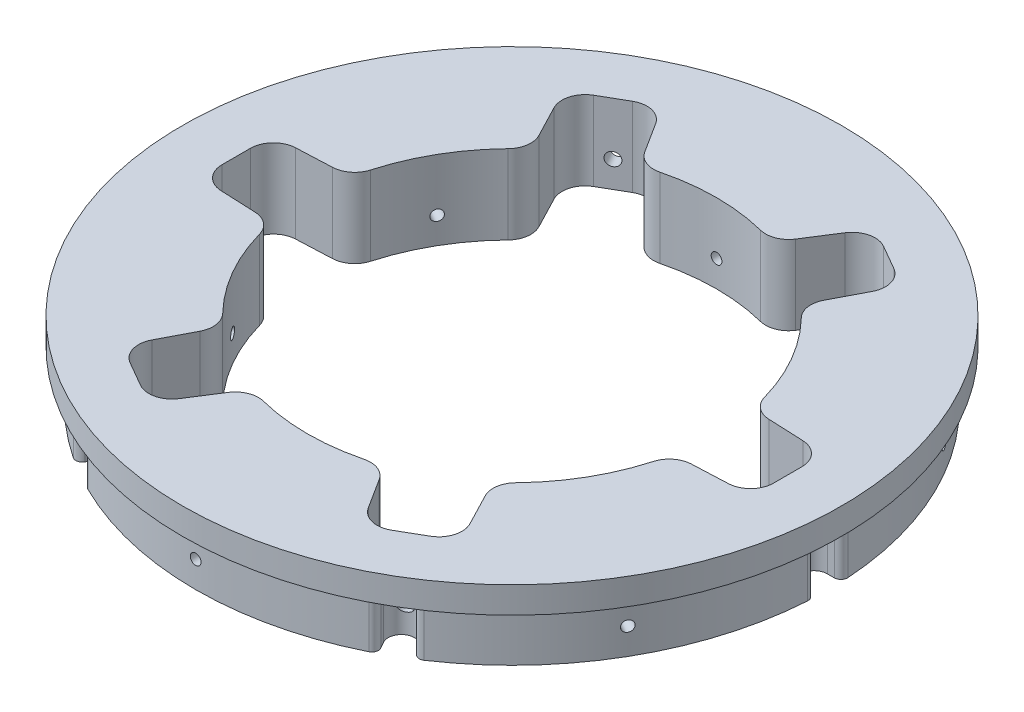
SolidWorks part; units mm, degrees
material "6061-T6 (SS)"
ref_plane "Front Plane" through (0, 0, 0) normal (0, 0, 1) x (1, 0, 0)
ref_plane "Top Plane" through (0, 0, 0) normal (0, 1, 0) x (1, 0, 0)
ref_plane "Right Plane" through (0, 0, 0) normal (1, 0, 0) x (0, 0, -1)
sketch "Sketch1" plane through (0, 0, 0) normal (0, 1, 0) x (1, 0, 0)
  circle A0 centre (0, 0) radius 76.2
  circle A1 centre (0, 0) radius 49.276
  dimension "D1" = 152.4
  dimension "D2" = 98.552
extrude "Boss-Extrude1" add sketch "Sketch1" against normal blind 19.05
sketch "Sketch3" plane through (0, -19.05, 0) normal (0, -1, 0) x (-1, 0, 0)
  line L0 (-76.1338, 3.175) -> (-72.771, 3.175)
  line L1 (-76.1338, -3.175) -> (-72.771, -3.175)
  circle A0 centre (0, 0) radius 76.2 construction
  arc A1 (-72.771, 3.175) -> (-72.771, -3.175) centre (-72.771, 0) cw
  arc A2 (-76.1338, -3.175) -> (-76.1338, 3.175) centre (0, 0) cw
  point P9 (-69.596, 0)
  point P13 (-76.2, 0)
  dimension "D1" = 6.35
  dimension "D2" = 6.604
extrude "Cut-Extrude1" cut sketch "Sketch3" against normal blind 12.7
sketch "Sketch4" plane through (0, -19.05, 0) normal (0, -1, 0) x (-1, 0, 0)
  line L0 (-66.421, 8.7312) -> (-66.421, -8.7312)
  line L1 (-66.421, -8.7312) -> (-48.3466, -9.525)
  line L2 (-48.3466, -9.525) -> (-48.3466, 9.525)
  line L3 (-48.3466, 9.525) -> (-66.421, 8.7312)
  line L4 (-66.421, 0) -> (0, 0) construction
  circle A0 centre (0, 0) radius 49.276 construction
  dimension "D1" = 3.175
  dimension "D2" = 19.05
  dimension "D3" = 17.4625
extrude "Cut-Extrude2" cut sketch "Sketch4" against normal through all
hole_wizard "1/8 (0.125) Diameter Hole2" positions "Sketch5" profile "Sketch6" hole size "1/8" standard "ANSI Inch" end condition through all
sketch "Sketch5" plane through (66.421, 0, 0) normal (-1, 0, 0) x (0, 0, 1)
  line L0 (-8.7312, -19.05) -> (8.7312, -19.05) construction
  point P0 (0, -12.7)
  dimension "D1" = 6.35
sketch "Sketch6" plane through (66.421, -12.7, 0) normal (0, 1, 0) x (0, 0, 1)
  line L0 (0, 0) -> (0, 9.779)
  line L1 (0, 9.779) -> (1.5875, 9.779)
  line L2 (1.5875, 9.779) -> (1.5875, 0)
  line L5 (1.5875, 0) -> (0, 0)
  line L11 (0, -6.35) -> (0, 107.95) construction
  dimension "Thru Hole Dia." = 3.175
  dimension "Thru Hole Depth" = 9.779
fillet "Fillet1" radius 1.5875 2 edges at (76.1338, -12.7, 3.175) (76.1338, -12.7, -3.175)
fillet "Fillet2" radius 5.5562 4 edges at (66.421, -9.525, 8.7312) (66.421, -9.525, -8.7312) (48.3466, -9.525, 9.525) (48.3466, -9.525, -9.525)
sketch "Sketch11" plane through (0, 0, 0) normal (0, 0, 1) x (1, 0, 0)
  line L0 (-76.2, -19.05) -> (76.0446, -19.05) construction
  circle A0 centre (0, -12.7) radius 1.2891
  dimension "D1" = 2.5781
  dimension "D2" = 6.35
extrude "Cut-Extrude4" cut sketch "Sketch11" against normal through all
pattern_circular "CirPattern1" count 6 over 360 about axis through (0, -19.05, 0) along (0, 1, 0) of "Cut-Extrude1", "Cut-Extrude2", "Fillet2", "Fillet1", "1/8 (0.125) Diameter Hole2", "Cut-Extrude4"
sketch "Sketch8" plane through (0, 0, 0) normal (0, 1, 0) x (1, 0, 0)
  circle A0 centre (0, 0) radius 79.375
  circle A1 centre (0, 0) radius 76.2
  circle A2 centre (0, 0) radius 76.2 construction
  dimension "D1" = 3.175
extrude "Boss-Extrude3" add sketch "Sketch8" against normal up to surface (6.35 mm away) up to face at (-74.0439, -6.35, 0)
